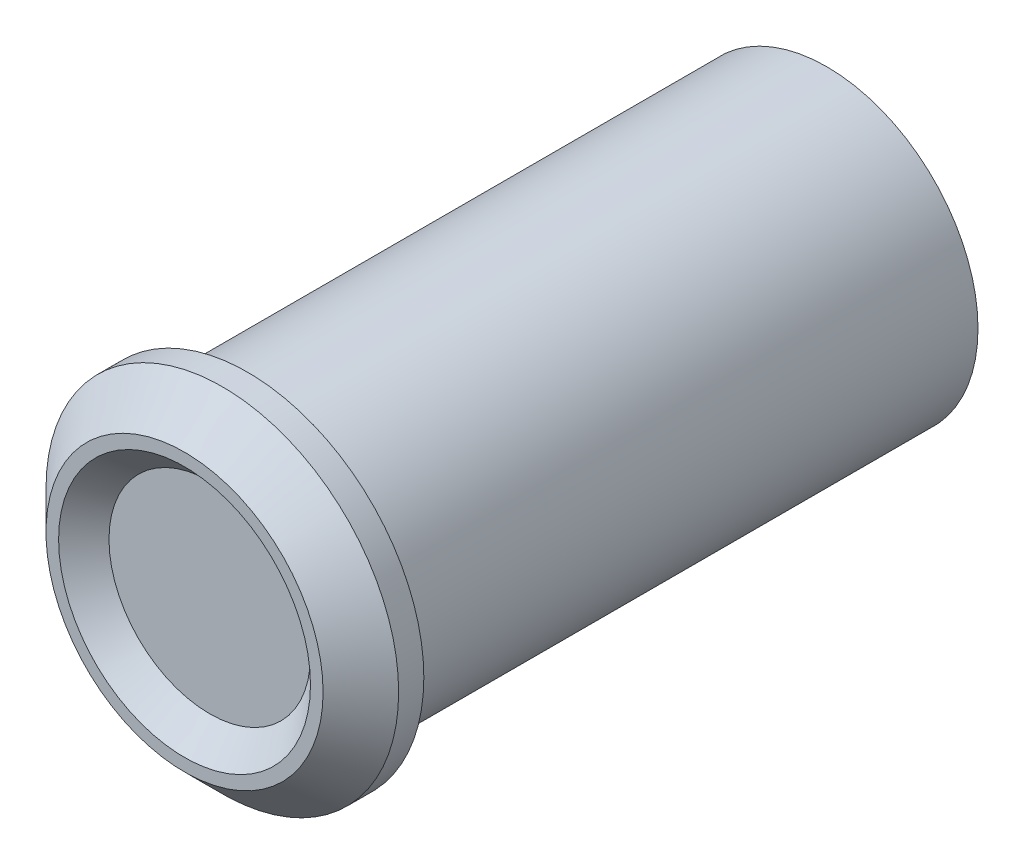
SolidWorks part; units mm, degrees
ref_plane "Front" through (0, 0, 0) normal (0, 0, 1) x (1, 0, 0)
ref_plane "Top" through (0, 0, 0) normal (0, 1, 0) x (1, 0, 0)
ref_plane "Right" through (0, 0, 0) normal (1, 0, 0) x (0, 0, -1)
sketch "Sketch1" plane through (0, 0, 0) normal (0, 0, 1) x (1, 0, 0)
  circle A0 centre (0, 0) radius 7
  dimension "D1" = 14
extrude "Boss-Extrude1" add sketch "Sketch1" along normal blind 1
sketch "Sketch2" plane through (0, 0, 1) normal (0, 0, 1) x (1, 0, 0)
  circle A1 centre (0, 0) radius 7
  circle A2 centre (0, 0) radius 7
  dimension "D1" = 0
extrude "Boss-Extrude2" add sketch "Sketch2" along normal blind 1.5 draft 45
sketch "Sketch3" plane through (0, 0, 2.5) normal (0, 0, 1) x (1, 0, 0)
  circle A2 centre (0, 0) radius 5
  circle A3 centre (0, 0) radius 5
  dimension "D1" = 0.5
extrude "Cut-Extrude1" cut sketch "Sketch3" against normal blind 1 draft 45
sketch "Sketch4" plane through (0, 0, 0) normal (0, 0, 1) x (1, 0, 0)
  circle A0 centre (0, 0) radius 6
  dimension "D1" = 12
extrude "Boss-Extrude3" add sketch "Sketch4" against normal blind 23
sketch "Panel Cut Guide" plane through (0, 0, 0) normal (0, 0, 1) x (1, 0, 0)
  circle A0 centre (0, 0) radius 6.05
  dimension "D1" = 12.1
